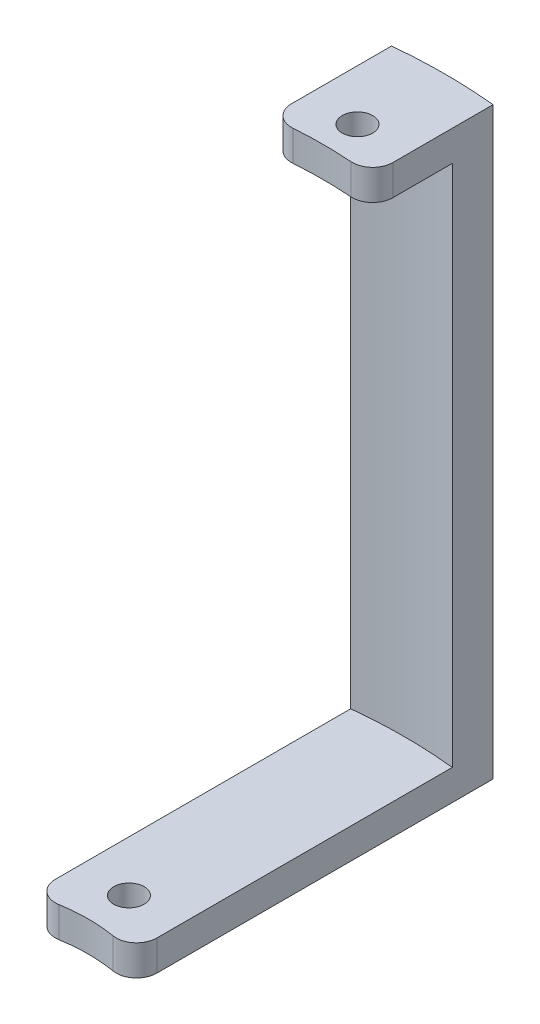
SolidWorks part; units mm, degrees
ref_plane "Front Plane" through (0, 0, 0) normal (0, 0, 1) x (1, 0, 0)
ref_plane "Top Plane" through (0, 0, 0) normal (0, 1, 0) x (1, 0, 0)
ref_plane "Right Plane" through (0, 0, 0) normal (1, 0, 0) x (0, 0, -1)
sketch "Sketch1" plane through (0, 0, 0) normal (0, 1, 0) x (1, 0, 0)
  line L0 (-5, 50.8548) -> (-5, 15.1987)
  line L1 (5, 50.8548) -> (5, 15.1987)
  circle A0 centre (0, 0) radius 42.5 construction
  circle A1 centre (0, 0) radius 45.85 construction
  circle A2 centre (0, 42.5) radius 1.5
  circle A3 centre (0, 20) radius 1.5
  arc A4 (-5, 15.1987) -> (5, 15.1987) centre (0, 0) cw
  arc A5 (5, 50.8548) -> (-5, 50.8548) centre (0, 0) ccw
  arc A6 (5, 38.779) -> (-5, 38.779) centre (0, 0) ccw
  arc A7 (5, 46.8339) -> (-5, 46.8339) centre (0, 0) ccw
  point P16 (-4.6067, 5.7976)
  point P17 (4.4336, 4.4336)
  point P18 (4.3288, 4.3416)
  point P19 (0, 0)
  point P20 (-4, 43.4825)
  point P21 (0, 20)
  point P22 (0, 20)
  point P23 (0, 0)
  point P24 (5, 15.676)
  dimension "D1" = 3
  dimension "D2" = 4
  dimension "D3" = 1.25
  dimension "D4" = 8
  dimension "D6" = 85
  dimension "D5" = 10
  dimension "D7" = 91.7
  dimension "D9" = 3
  dimension "D10" = 16
  dimension "D8" = 20
extrude "Boss-Extrude1" add sketch "Sketch1" against normal blind 3 contours A7 L1 A5 L0 | L1 A7 L0 A6 A2 | A2 | L1 A6 L0 A4 A3 region at (0, 0, -49.0147) region at (0, 0, -46.9699) region at (0, 0, -27.5942) region at (0, 0, -42.5)
extrude "Boss-Extrude2" add sketch "Sketch1<3>" along normal blind 51.5 contours A7 L1 A5 L0 region at (0, 0, -49.0147)
sketch "Sketch1<3>" plane through (0, 0, 0) normal (0, 1, 0) x (1, 0, 0) same geometry as "Sketch1"
extrude "Boss-Extrude3" add sketch "Sketch1<4>" along normal blind 3 from offset 51.5 contours L1 A7 L0 A6 A2 | A7 L1 A5 L0 region at (0, 0, -49.0147) region at (0, 0, -46.9699)
sketch "Sketch1<4>" plane through (0, 0, 0) normal (0, 1, 0) x (1, 0, 0) same geometry as "Sketch1"
fillet "Fillet1" radius 2 4 edges at (-5, 53, -38.779) (5, 53, -38.779) (5, -1.5, -15.1987) (-5, -1.5, -15.1987)
